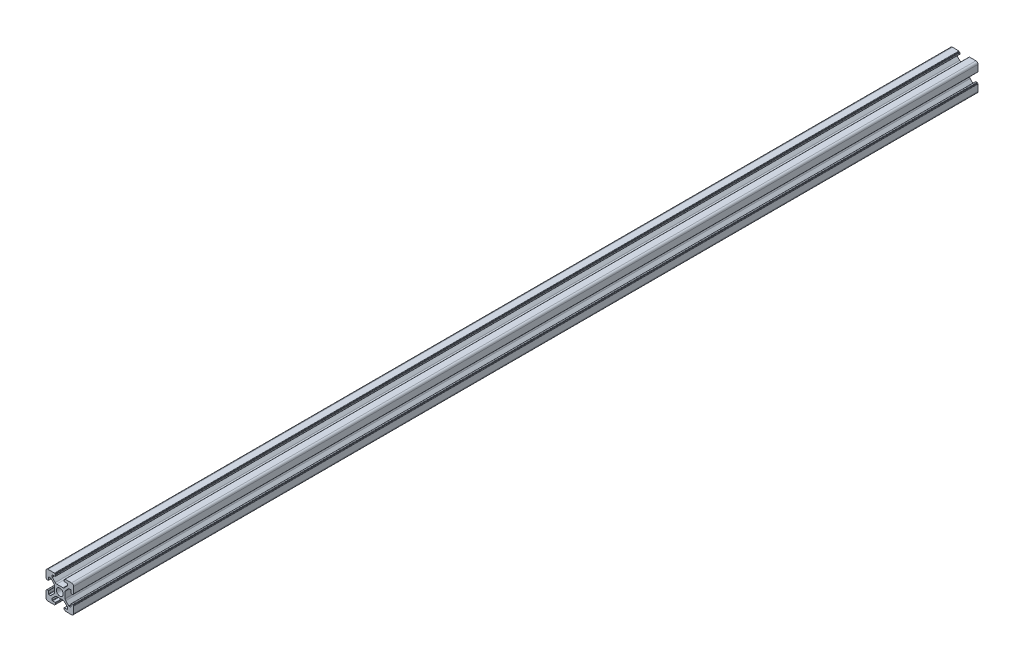
SolidWorks part; units mm, degrees
ref_plane "前视基准面" through (0, 0, 0) normal (0, 0, 1) x (1, 0, 0)
ref_plane "上视基准面" through (0, 0, 0) normal (0, 1, 0) x (1, 0, 0)
ref_plane "右视基准面" through (0, 0, 0) normal (1, 0, 0) x (0, 0, -1)
sketch "草图1" plane through (0, 0, 0) normal (0, 0, 1) x (1, 0, 0)
  line L0 (0, 0) -> (0, 5.5) construction
  line L1 (-8.5023, -10.0023) -> (-3.85, -10.0023)
  line L2 (-10.0023, -8.5023) -> (-10.0023, -3.85)
  line L3 (-8.5023, 10.0023) -> (-3.85, 10.0023)
  line L4 (10.0023, -8.5023) -> (10.0023, -3.85)
  line L5 (-10.0023, -10.0023) -> (10.0023, 10.0023) construction
  line L6 (-10.0023, 10.0023) -> (10.0023, -10.0023) construction
  line L7 (-2.218, -3.9) -> (2.218, -3.9)
  line L8 (-3.9, -2.218) -> (-3.9, 2.218)
  line L9 (-2.218, 3.9) -> (2.218, 3.9)
  line L10 (3.9, -2.218) -> (3.9, 2.218)
  line L11 (-3.9, -3.9) -> (3.9, 3.9) construction
  line L12 (-3.9, 3.9) -> (3.9, -3.9) construction
  line L13 (-5.25, -8.2) -> (-3.35, -8.2)
  line L14 (-8.2, -5.25) -> (-8.2, -3.35)
  line L15 (-5.25, 8.2) -> (-3.35, 8.2)
  line L16 (8.2, -5.25) -> (8.2, -3.35)
  line L17 (-8.2, -8.2) -> (8.2, 8.2) construction
  line L18 (-8.2, 8.2) -> (8.2, -8.2) construction
  line L19 (-7.95, 5.5) -> (-6.6642, 5.5)
  line L20 (0, 0) -> (5.5, 0) construction
  line L23 (-5.5, 7.95) -> (-5.5, 6.6642)
  line L26 (0, 0) -> (-0.5303, 0.5303)
  line L27 (3.2787, 4.3393) -> (5.4268, 6.4874)
  line L28 (0, 0) -> (0.5303, -0.5303)
  line L29 (5.5, 6.6642) -> (5.5, 7.95)
  line L30 (4.3393, 3.2787) -> (6.4874, 5.4268)
  line L31 (6.6642, 5.5) -> (7.95, 5.5)
  line L32 (4.3393, -3.2787) -> (6.4874, -5.4268)
  line L33 (3.2787, -4.3393) -> (5.4268, -6.4874)
  line L34 (-3.2787, -4.3393) -> (-5.4268, -6.4874)
  line L35 (-4.3393, -3.2787) -> (-6.4874, -5.4268)
  line L36 (-4.3393, 3.2787) -> (-6.4874, 5.4268)
  line L37 (-3.2787, 4.3393) -> (-5.4268, 6.4874)
  line L38 (3.1, -8.45) -> (3.1, -9.2523)
  line L39 (8.45, 3.1) -> (9.2523, 3.1)
  line L40 (-5.5, -6.6642) -> (-5.5, -7.95)
  line L41 (-6.6642, -5.5) -> (-7.95, -5.5)
  line L42 (5.5, -6.6642) -> (5.5, -7.95)
  line L43 (6.6642, -5.5) -> (7.95, -5.5)
  line L44 (9.2523, -3.1) -> (8.45, -3.1)
  line L46 (10.0023, 3.85) -> (10.0023, 8.5023)
  line L47 (8.2, 3.35) -> (8.2, 5.25)
  line L48 (-3.1, -9.2523) -> (-3.1, -8.45)
  line L49 (-8.45, -3.1) -> (-9.2523, -3.1)
  line L50 (-9.2523, 3.1) -> (-8.45, 3.1)
  line L51 (-3.1, 8.45) -> (-3.1, 9.2523)
  line L52 (3.1, 9.2523) -> (3.1, 8.45)
  line L53 (3.85, 10.0023) -> (8.5023, 10.0023)
  line L54 (3.35, 8.2) -> (5.25, 8.2)
  line L55 (-10.0023, 3.85) -> (-10.0023, 8.5023)
  line L56 (-8.2, 3.35) -> (-8.2, 5.25)
  line L57 (3.35, -8.2) -> (5.25, -8.2)
  line L58 (3.85, -10.0023) -> (8.5023, -10.0023)
  line L59 (9.7523, -3.6) -> (9.5023, -3.6)
  line L61 (9.7523, 3.6) -> (9.5023, 3.6)
  line L62 (9.5023, -3.6) -> (9.5023, -3.35)
  line L63 (3.6, -9.7523) -> (3.6, -9.5023)
  line L64 (3.35, -9.5023) -> (3.6, -9.5023)
  line L65 (9.5023, 3.35) -> (9.5023, 3.6)
  line L66 (-3.6, -9.5023) -> (-3.35, -9.5023)
  line L67 (-3.6, -9.7523) -> (-3.6, -9.5023)
  line L68 (-9.7523, -3.6) -> (-9.5023, -3.6)
  line L69 (-9.5023, -3.35) -> (-9.5023, -3.6)
  line L70 (-9.5023, 3.6) -> (-9.5023, 3.35)
  line L71 (-9.7523, 3.6) -> (-9.5023, 3.6)
  line L72 (-3.6, 9.7523) -> (-3.6, 9.5023)
  line L73 (-3.35, 9.5023) -> (-3.6, 9.5023)
  line L74 (3.6, 9.5023) -> (3.35, 9.5023)
  line L75 (3.6, 9.7523) -> (3.6, 9.5023)
  circle A0 centre (0, 0) radius 2.5
  arc A1 (10.0023, 8.5023) -> (8.5023, 10.0023) centre (8.5023, 8.5023) ccw
  arc A2 (8.5023, -10.0023) -> (10.0023, -8.5023) centre (8.5023, -8.5023) ccw
  arc A3 (-10.0023, -8.5023) -> (-8.5023, -10.0023) centre (-8.5023, -8.5023) ccw
  arc A4 (-10.0023, 8.5023) -> (-8.5023, 10.0023) centre (-8.5023, 8.5023) cw
  arc A5 (-9.5023, -3.35) -> (-9.2523, -3.1) centre (-9.2523, -3.35) cw
  arc A6 (-9.7523, -3.6) -> (-10.0023, -3.85) centre (-9.7523, -3.85) ccw
  arc A7 (-8.45, -3.1) -> (-8.2, -3.35) centre (-8.45, -3.35) cw
  arc A8 (-7.95, -5.5) -> (-8.2, -5.25) centre (-7.95, -5.25) cw
  arc A9 (-6.4874, -5.4268) -> (-6.6642, -5.5) centre (-6.6642, -5.25) cw
  arc A10 (-5.4268, -6.4874) -> (-5.5, -6.6642) centre (-5.25, -6.6642) ccw
  arc A11 (-5.5, -7.95) -> (-5.25, -8.2) centre (-5.25, -7.95) ccw
  arc A12 (-3.6, -9.7523) -> (-3.85, -10.0023) centre (-3.85, -9.7523) cw
  arc A13 (-3.35, -9.5023) -> (-3.1, -9.2523) centre (-3.35, -9.2523) ccw
  arc A14 (-3.1, -8.45) -> (-3.35, -8.2) centre (-3.35, -8.45) ccw
  arc A15 (3.1, -8.45) -> (3.35, -8.2) centre (3.35, -8.45) cw
  arc A16 (5.5, -7.95) -> (5.25, -8.2) centre (5.25, -7.95) cw
  arc A17 (5.4268, -6.4874) -> (5.5, -6.6642) centre (5.25, -6.6642) cw
  arc A18 (6.4874, -5.4268) -> (6.6642, -5.5) centre (6.6642, -5.25) ccw
  arc A19 (7.95, -5.5) -> (8.2, -5.25) centre (7.95, -5.25) ccw
  arc A20 (8.45, -3.1) -> (8.2, -3.35) centre (8.45, -3.35) ccw
  arc A21 (9.5023, -3.35) -> (9.2523, -3.1) centre (9.2523, -3.35) ccw
  arc A22 (9.7523, -3.6) -> (10.0023, -3.85) centre (9.7523, -3.85) cw
  arc A23 (3.35, -9.5023) -> (3.1, -9.2523) centre (3.35, -9.2523) cw
  arc A24 (3.6, -9.7523) -> (3.85, -10.0023) centre (3.85, -9.7523) ccw
  arc A25 (7.95, 5.5) -> (8.2, 5.25) centre (7.95, 5.25) cw
  arc A26 (8.2, 3.35) -> (8.45, 3.1) centre (8.45, 3.35) ccw
  arc A27 (9.5023, 3.35) -> (9.2523, 3.1) centre (9.2523, 3.35) cw
  arc A28 (9.7523, 3.6) -> (10.0023, 3.85) centre (9.7523, 3.85) ccw
  arc A29 (6.6642, 5.5) -> (6.4874, 5.4268) centre (6.6642, 5.25) ccw
  arc A30 (5.4268, 6.4874) -> (5.5, 6.6642) centre (5.25, 6.6642) ccw
  arc A31 (5.5, 7.95) -> (5.25, 8.2) centre (5.25, 7.95) ccw
  arc A32 (3.1, 8.45) -> (3.35, 8.2) centre (3.35, 8.45) ccw
  arc A33 (3.6, 9.7523) -> (3.85, 10.0023) centre (3.85, 9.7523) cw
  arc A34 (3.35, 9.5023) -> (3.1, 9.2523) centre (3.35, 9.2523) ccw
  arc A35 (-9.7523, 3.6) -> (-10.0023, 3.85) centre (-9.7523, 3.85) cw
  arc A36 (-9.5023, 3.35) -> (-9.2523, 3.1) centre (-9.2523, 3.35) ccw
  arc A37 (-8.45, 3.1) -> (-8.2, 3.35) centre (-8.45, 3.35) ccw
  arc A38 (-8.2, 5.25) -> (-7.95, 5.5) centre (-7.95, 5.25) cw
  arc A39 (-6.4874, 5.4268) -> (-6.6642, 5.5) centre (-6.6642, 5.25) ccw
  arc A40 (-5.4268, 6.4874) -> (-5.5, 6.6642) centre (-5.25, 6.6642) cw
  arc A41 (-5.5, 7.95) -> (-5.25, 8.2) centre (-5.25, 7.95) cw
  arc A42 (-3.1, 8.45) -> (-3.35, 8.2) centre (-3.35, 8.45) cw
  arc A43 (-3.1, 9.2523) -> (-3.35, 9.5023) centre (-3.35, 9.2523) ccw
  arc A44 (-3.6, 9.7523) -> (-3.85, 10.0023) centre (-3.85, 9.7523) ccw
  arc A45 (-4.3393, 3.2787) -> (-3.9, 2.218) centre (-5.4, 2.218) cw
  arc A46 (-3.2787, 4.3393) -> (-2.218, 3.9) centre (-2.218, 5.4) ccw
  arc A47 (3.2787, 4.3393) -> (2.218, 3.9) centre (2.218, 5.4) cw
  arc A48 (4.3393, 3.2787) -> (3.9, 2.218) centre (5.4, 2.218) ccw
  arc A49 (4.3393, -3.2787) -> (3.9, -2.218) centre (5.4, -2.218) cw
  arc A50 (3.2787, -4.3393) -> (2.218, -3.9) centre (2.218, -5.4) ccw
  arc A51 (-4.3393, -3.2787) -> (-3.9, -2.218) centre (-5.4, -2.218) ccw
  arc A52 (-2.218, -3.9) -> (-3.2787, -4.3393) centre (-2.218, -5.4) ccw
  point P0 (0, 0)
  point P7 (10.0023, 0)
  point P62 (0, 0)
  point P76 (0, 0)
  point P92 (-8.2, -5.5)
  point P99 (0, 0)
  point P106 (-5.5, -8.2)
  point P117 (5.5, -8.2)
  point P124 (8.2, -5.5)
  point P137 (8.2, 5.5)
  point P140 (8.2, 3.1)
  point P147 (6.5607, 5.5)
  point P152 (5.5, 8.2)
  point P167 (-8.2, 5.5)
  point P174 (-5.5, 8.2)
  dimension "D1" = 1.5
  dimension "D5" = 0.25
  dimension "D6" = 1.5
  dimension "D2" = 4
  dimension "D3" = 4
  dimension "D4" = 4
extrude "凸台-拉伸1" add sketch "草图1" along normal blind 1220 contours A52 L7 A50 L33 A17 L42 A16 L57 A15 L38 A23 L64 L63 A24 L58 A2 L4 A22 L59 L62 A21 L44 A20 L16 A19 L43 A18 L32 A49 L10 A48 L30 A29 L31 A25 L47 A26 L39 A27 L65 L61 A28 L46 A1 L53 A33 L75 L74 A34 L52 A32 region at (-9.3629, -9.3629, 0)
ref_plane "Plane1" through (0, 0, 564) normal (0, 0, 1) x (1, 0, 0)
sketch "Sketch1" plane through (0, 0, 564) normal (0, 0, 1) x (1, 0, 0)
  circle A0 centre (0, 0) radius 16.7715
extrude "Cut-Extrude1" cut sketch "Sketch1" against normal through all
ref_plane "CenterPlane" through (0, 0, 892) normal (0, 0, 1) x (1, 0, 0)
